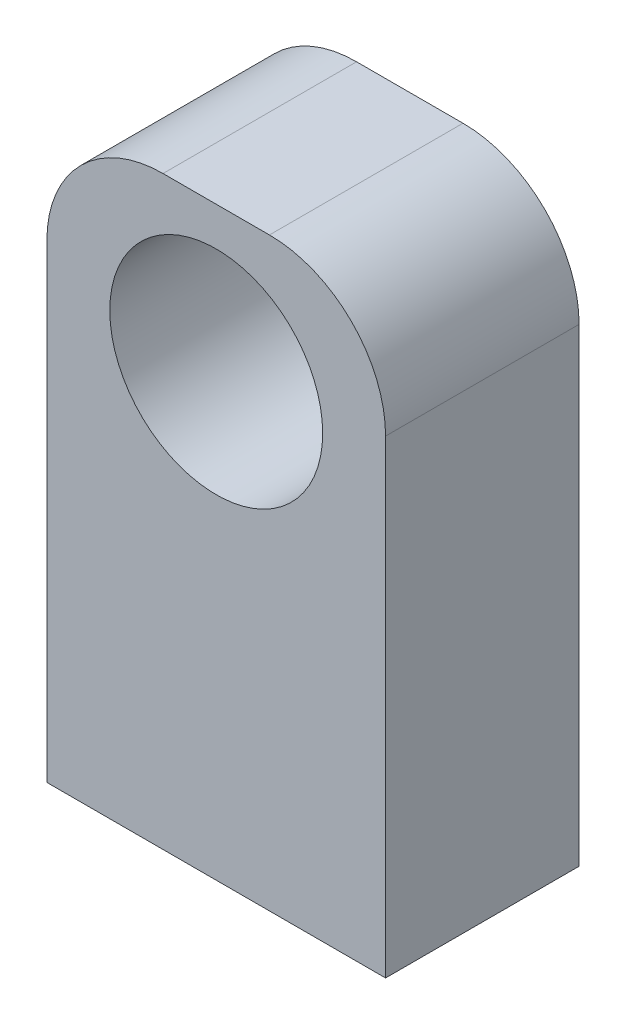
SolidWorks part; units mm, degrees
ref_plane "Front Plane" through (0, 0, 0) normal (0, 0, 1) x (1, 0, 0)
ref_plane "Top Plane" through (0, 0, 0) normal (0, 1, 0) x (1, 0, 0)
ref_plane "Right Plane" through (0, 0, 0) normal (1, 0, 0) x (0, 0, -1)
sketch "Sketch1" plane through (0, 0, 0) normal (0, 1, 0) x (1, 0, 0)
  line L1 (-16.3353, 9.1448) -> (18.6647, 9.1448)
  line L2 (-16.3353, 9.1448) -> (-16.3353, -10.8552)
  line L3 (-16.3353, -10.8552) -> (18.6647, -10.8552)
  line L4 (18.6647, 9.1448) -> (18.6647, -10.8552)
  dimension "D1" = 35
  dimension "D2" = 20
extrude "Boss-Extrude1" add sketch "Sketch1" along normal blind 60.5
sketch "Sketch2" plane through (0, 0, 10.8552) normal (0, 0, 1) x (1, 0, 0)
  line L0 (18.6647, 60.5) -> (18.6647, 0) construction
  line L2 (-16.3353, 60.5) -> (18.6647, 60.5) construction
  circle A0 centre (1.1647, 45.5) radius 11
  dimension "D1" = 17.5
  dimension "D2" = 15
extrude "Cut-Extrude1" cut sketch "Sketch2" against normal through all
sketch "Sketch3" plane through (0, 0, 0) normal (0, -1, 0) x (1, 0, 0)
  line L0 (18.6647, -9.1448) -> (-16.3353, -9.1448) construction
  line L1 (-16.3353, -9.1448) -> (-16.3353, 10.8552) construction
  line L2 (18.6647, 10.8552) -> (18.6647, -9.1448) construction
  circle A0 centre (-8.3353, 0.8552) radius 1.75
  circle A1 centre (10.6647, 0.8552) radius 1.75
  point P4 (-16.3353, 0.8552)
  dimension "D1" = 10
  dimension "D3" = 10
  dimension "D2" = 8
  dimension "D4" = 8
extrude "Cut-Extrude2" cut sketch "Sketch3" against normal blind 10
fillet "Fillet1" radius 12 2 edges at (18.6647, 60.5, 0.8552) (-16.3353, 60.5, 0.8552)
